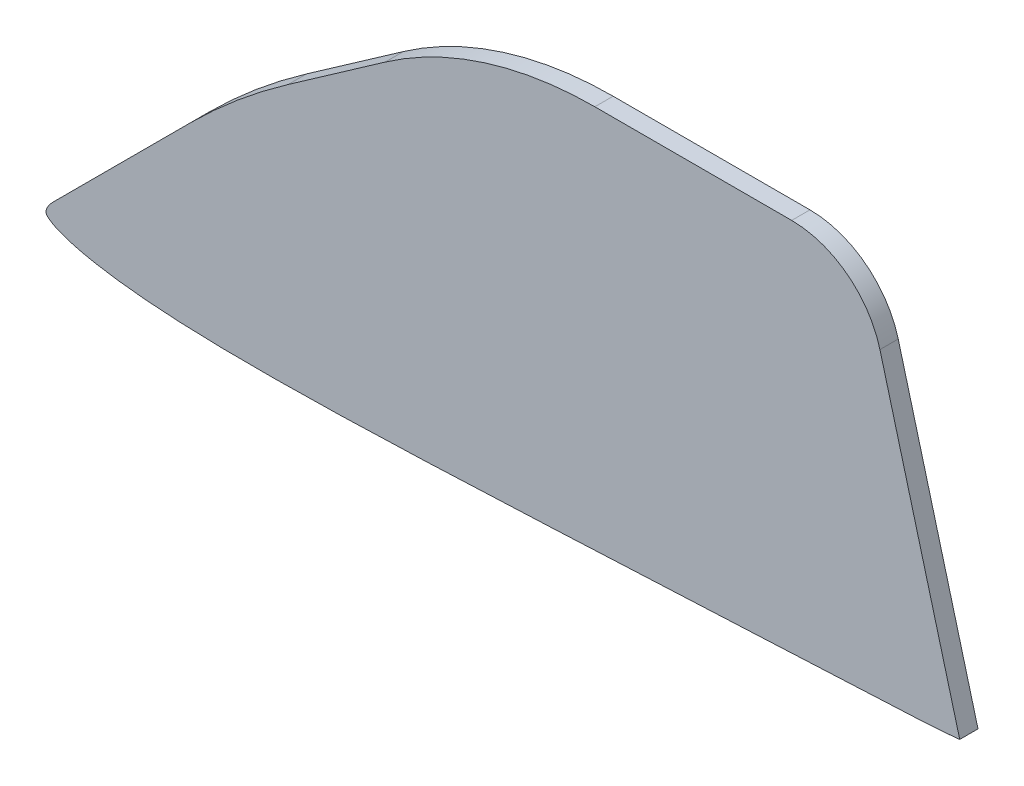
SolidWorks part; units mm, degrees
ref_plane "Front Plane" through (0, 0, 0) normal (0, 0, 1) x (1, 0, 0)
ref_plane "Top Plane" through (0, 0, 0) normal (0, 1, 0) x (1, 0, 0)
ref_plane "Right Plane" through (0, 0, 0) normal (1, 0, 0) x (0, 0, -1)
curve "Curve1"
  spline degree 3 poles (319.3399, -0.0631, 0) (320.1749, 0.0121, 0) (319.2775, -0.0304, 0) (318.5408, -0.0213, 0) (316.7306, 0.0124, 0) (314.5198, 0.1434, 0) (311.6513, 0.3645, 0) (308.3098, 0.7064, 0) (304.5223, 1.1688, 0) (300.3775, 1.7342, 0) (295.943, 2.3803, 0) (291.2893, 3.0786, 0) (286.4795, 3.7953, 0) (281.5654, 4.4835, 0) (276.5911, 5.1112, 0) (271.5953, 5.6552, 0) (266.6171, 6.1013, 0) (261.6991, 6.4472, 0) (256.8868, 6.6894, 0) (252.2271, 6.822, 0) (247.7645, 6.8415, 0) (243.539, 6.7385, 0) (239.586, 6.5122, 0) (235.9364, 6.165, 0) (232.6179, 5.7039, 0) (229.6553, 5.1389, 0) (227.0686, 4.4832, 0) (224.8731, 3.7453, 0) (223.0782, 2.9469, 0) (221.6854, 2.1189, 0) (220.7273, 1.3252, 0) (220.2338, 0.7064, 0) (220.0616, 0.3184, 0) (220.0116, 0.1395, 0) (219.9959, -0.0029, 0) (220.0081, -0.1155, 0) (220.062, -0.2184, 0) (220.1603, -0.338, 0) (220.3145, -0.4779, 0) (220.4826, -0.5989, 0) (220.9421, -0.8937, 0) (221.8924, -1.2976, 0) (223.5205, -1.784, 0) (225.624, -2.2279, 0) (228.1771, -2.6133, 0) (231.1641, -2.9192, 0) (234.5635, -3.137, 0) (238.352, -3.2671, 0) (242.4996, -3.312, 0) (246.9689, -3.2849, 0) (251.716, -3.1932, 0) (256.6914, -3.0476, 0) (261.8415, -2.8575, 0) (267.1088, -2.6383, 0) (272.4315, -2.3988, 0) (277.7457, -2.1515, 0) (282.9865, -1.902, 0) (288.0894, -1.6584, 0) (292.9917, -1.4233, 0) (297.6334, -1.202, 0) (301.9578, -0.9952, 0) (305.9103, -0.8085, 0) (309.4451, -0.64, 0) (312.5051, -0.4927, 0) (315.0892, -0.3596, 0) (317.0641, -0.2502, 0) (318.6672, -0.1355, 0) (319.3399, -0.0631, 0) (320.1749, 0.0121, 0) (319.2775, -0.0304, 0) knots -0.013413 -0.006112 -0.001576 0 0.001644 0.006617 0.014862 0.026171 0.040322 0.057038 0.075955 0.096697 0.118903 0.142213 0.166278 0.190806 0.215581 0.240407 0.265107 0.28948 0.3133 0.336346 0.3584 0.379278 0.398833 0.416933 0.433472 0.448354 0.461506 0.472899 0.482558 0.490505 0.496775 0.500889 0.502032 0.503032 0.503621 0.504144 0.50468 0.505311 0.506426 0.507746 0.50837 0.514497 0.522892 0.533497 0.546244 0.561059 0.577879 0.596602 0.617103 0.639204 0.662686 0.687305 0.712801 0.738887 0.765254 0.791583 0.817549 0.842832 0.867121 0.890118 0.911544 0.931132 0.948636 0.963834 0.976537 0.986587 0.993888 0.998424 1 1.001644 1.006617 1.014862 periodic
sketch "Sketch1" plane through (0, 0, 0) normal (0, 0, 1) x (1, 0, 0)
  line L0 (320, 0) -> (320, 24.575) construction
  line L1 (220.7656, 1.3114) -> (240.7656, 21.3114)
  line L2 (240.7656, 21.3114) -> (267.4557, 40)
  line L3 (309.282, 40) -> (320, 0)
  line L4 (220.7656, 1.3114) -> (220.7656, 28.3519) construction
  line L5 (267.4557, 40) -> (309.282, 40)
  spline S0 degree 3 poles (319.3399, -0.0631) (320.1749, 0.0121) (319.2775, -0.0304) (318.5408, -0.0213) (316.7306, 0.0124) (314.5198, 0.1434) (311.6513, 0.3645) (308.3098, 0.7064) (304.5223, 1.1688) (300.3775, 1.7342) (295.943, 2.3803) (291.2893, 3.0786) (286.4795, 3.7953) (281.5654, 4.4835) (276.5911, 5.1112) (271.5953, 5.6552) (266.6171, 6.1013) (261.6991, 6.4472) (256.8868, 6.6894) (252.2271, 6.822) (247.7645, 6.8415) (243.539, 6.7385) (239.586, 6.5122) (235.9364, 6.165) (232.6179, 5.7039) (229.6553, 5.1389) (227.0686, 4.4832) (224.8731, 3.7453) (223.0782, 2.9469) (221.6854, 2.1189) (220.7273, 1.3252) (220.2338, 0.7064) (220.0616, 0.3184) (220.0116, 0.1395) (219.9959, -0.0029) (220.0081, -0.1155) (220.062, -0.2184) (220.1603, -0.338) (220.3145, -0.4779) (220.4826, -0.5989) (220.9421, -0.8937) (221.8924, -1.2976) (223.5205, -1.784) (225.624, -2.2279) (228.1771, -2.6133) (231.1641, -2.9192) (234.5635, -3.137) (238.352, -3.2671) (242.4996, -3.312) (246.9689, -3.2849) (251.716, -3.1932) (256.6914, -3.0476) (261.8415, -2.8575) (267.1088, -2.6383) (272.4315, -2.3988) (277.7457, -2.1515) (282.9865, -1.902) (288.0894, -1.6584) (292.9917, -1.4233) (297.6334, -1.202) (301.9578, -0.9952) (305.9103, -0.8085) (309.4451, -0.64) (312.5051, -0.4927) (315.0892, -0.3596) (317.0641, -0.2502) (318.6672, -0.1355) (319.3399, -0.0631) (320.1749, 0.0121) (319.2775, -0.0304) knots -0.013413 -0.006112 -0.001576 0 0.001644 0.006617 0.014862 0.026171 0.040322 0.057038 0.075955 0.096697 0.118903 0.142213 0.166278 0.190806 0.215581 0.240407 0.265107 0.28948 0.3133 0.336346 0.3584 0.379278 0.398833 0.416933 0.433472 0.448354 0.461506 0.472899 0.482558 0.490505 0.496775 0.500889 0.502032 0.503032 0.503621 0.504144 0.50468 0.505311 0.506426 0.507746 0.50837 0.514497 0.522892 0.533497 0.546244 0.561059 0.577879 0.596602 0.617103 0.639204 0.662686 0.687305 0.712801 0.738887 0.765254 0.791583 0.817549 0.842832 0.867121 0.890118 0.911544 0.931132 0.948636 0.963834 0.976537 0.986587 0.993888 0.998424 1 1.001644 1.006617 1.014862 only from (320, 0) to (320, 0) construction
  spline S1 degree 3 poles (319.3399, -0.0631) (320.1749, 0.0121) (319.2775, -0.0304) (318.5408, -0.0213) (316.7306, 0.0124) (314.5198, 0.1434) (311.6513, 0.3645) (308.3098, 0.7064) (304.5223, 1.1688) (300.3775, 1.7342) (295.943, 2.3803) (291.2893, 3.0786) (286.4795, 3.7953) (281.5654, 4.4835) (276.5911, 5.1112) (271.5953, 5.6552) (266.6171, 6.1013) (261.6991, 6.4472) (256.8868, 6.6894) (252.2271, 6.822) (247.7645, 6.8415) (243.539, 6.7385) (239.586, 6.5122) (235.9364, 6.165) (232.6179, 5.7039) (229.6553, 5.1389) (227.0686, 4.4832) (224.8731, 3.7453) (223.0782, 2.9469) (221.6854, 2.1189) (220.7273, 1.3252) (220.2338, 0.7064) (220.0616, 0.3184) (220.0116, 0.1395) (219.9959, -0.0029) (220.0081, -0.1155) (220.062, -0.2184) (220.1603, -0.338) (220.3145, -0.4779) (220.4826, -0.5989) (220.9421, -0.8937) (221.8924, -1.2976) (223.5205, -1.784) (225.624, -2.2279) (228.1771, -2.6133) (231.1641, -2.9192) (234.5635, -3.137) (238.352, -3.2671) (242.4996, -3.312) (246.9689, -3.2849) (251.716, -3.1932) (256.6914, -3.0476) (261.8415, -2.8575) (267.1088, -2.6383) (272.4315, -2.3988) (277.7457, -2.1515) (282.9865, -1.902) (288.0894, -1.6584) (292.9917, -1.4233) (297.6334, -1.202) (301.9578, -0.9952) (305.9103, -0.8085) (309.4451, -0.64) (312.5051, -0.4927) (315.0892, -0.3596) (317.0641, -0.2502) (318.6672, -0.1355) (319.3399, -0.0631) (320.1749, 0.0121) (319.2775, -0.0304) knots -0.013413 -0.006112 -0.001576 0 0.001644 0.006617 0.014862 0.026171 0.040322 0.057038 0.075955 0.096697 0.118903 0.142213 0.166278 0.190806 0.215581 0.240407 0.265107 0.28948 0.3133 0.336346 0.3584 0.379278 0.398833 0.416933 0.433472 0.448354 0.461506 0.472899 0.482558 0.490505 0.496775 0.500889 0.502032 0.503032 0.503621 0.504144 0.50468 0.505311 0.506426 0.507746 0.50837 0.514497 0.522892 0.533497 0.546244 0.561059 0.577879 0.596602 0.617103 0.639204 0.662686 0.687305 0.712801 0.738887 0.765254 0.791583 0.817549 0.842832 0.867121 0.890118 0.911544 0.931132 0.948636 0.963834 0.976537 0.986587 0.993888 0.998424 1 1.001644 1.006617 1.014862 only from (320, 0) to (320, 0)
  point P8 (305.1806, 50.1718)
  point P9 (304.0914, 50.1718)
  dimension "D1" = 45
  dimension "D2" = 20
  dimension "D3" = 55
  dimension "D4" = 15
  dimension "D5" = 40
extrude "Boss-Extrude1" add sketch "Sketch1" along normal blind 2 contours S1 | S1 region at (279.7537, 19.7994, 0) region at (259.0166, 1.412, 0)
fillet "Fillet2" radius 10 1 edges at (309.282, 40, 1)
fillet "Fillet3" radius 40 1 edges at (267.4557, 40, 1)
fillet "Fillet4" radius 80 1 edges at (240.7656, 21.3114, 1)
